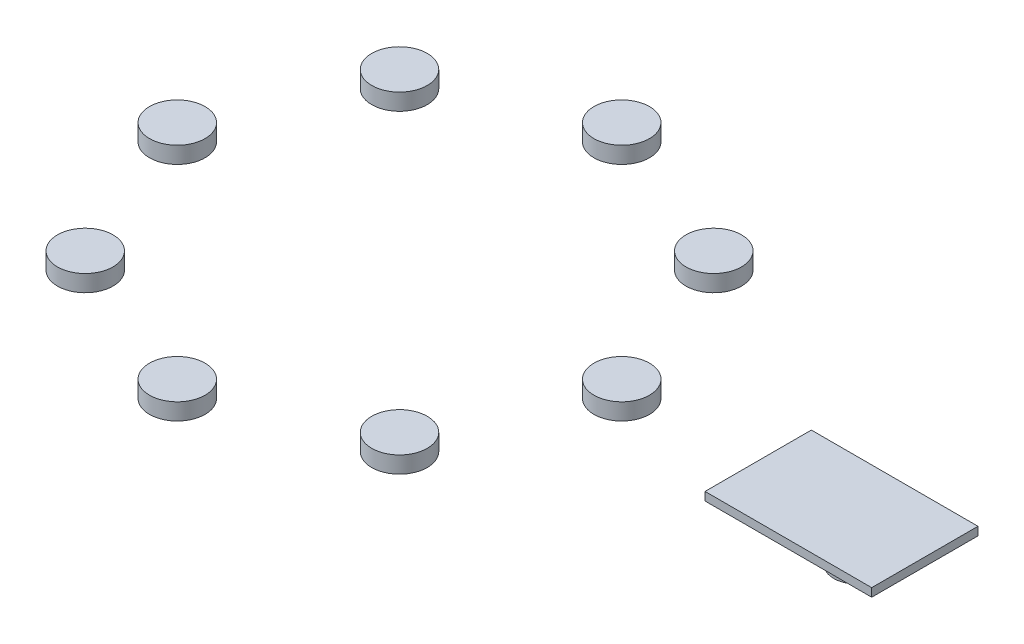
SolidWorks part; units mm, degrees
ref_plane "Front Plane" through (0, 0, 0) normal (0, 0, 1) x (1, 0, 0)
ref_plane "Top Plane" through (0, 0, 0) normal (0, 1, 0) x (1, 0, 0)
ref_plane "Right Plane" through (0, 0, 0) normal (1, 0, 0) x (0, 0, -1)
sketch "Sketch1" plane through (0, 0, 0) normal (0, 1, 0) x (1, 0, 0)
  line L0 (-37.5, 0) -> (-15, 0) construction
  line L7 (32.5, -5) -> (17.5, -5)
  line L8 (32.5, -5) -> (32.5, 4.5667)
  line L9 (32.5, 4.5667) -> (17.5, 4.5667)
  line L10 (17.5, -5) -> (17.5, 4.5667)
  line L11 (32.5, -5) -> (17.5, 4.5667) construction
  line L12 (32.5, 4.5667) -> (17.5, -5) construction
  circle A0 centre (-35, 0) radius 2.5
  circle A2 centre (-29.1421, 14.1421) radius 2.5
  circle A3 centre (-15, 20) radius 2.5
  circle A4 centre (-0.8579, 14.1421) radius 2.5
  circle A5 centre (5, 0) radius 2.5
  circle A6 centre (-0.8579, -14.1421) radius 2.5
  circle A7 centre (-15, -20) radius 2.5
  circle A8 centre (-29.1421, -14.1421) radius 2.5
  point P0 (0, 0)
  point P6 (25, -0.2166)
  dimension "D3" = 5
  dimension "D6" = 22.5
  dimension "D9" = 15
  dimension "D7" = 8
extrude "Boss-Extrude3" add sketch "Sketch1" along normal blind 1.5 contours A5 | A7 | A8 | A0 | L10 L7 L8 L9 | A2 | A3 | A4 | A6 region at (25, 0, 0.2166) region at (-35, 0, 0) region at (-29.1421, 0, -14.1421) region at (5, 0, 0) region at (-15, 0, 20) region at (-29.1421, 0, 14.1421)
sketch "Sketch2" plane through (0, 0, 0) normal (0, -1, 0) x (1, 0, 0)
  line L0 (17.5, -4.5667) -> (32.5, 5)
  line L1 (32.5, 5) -> (17.5, 5) construction
  line L2 (32.5, 5) -> (32.5, -4.5667) construction
  line L3 (32.5, -4.5667) -> (17.5, -4.5667) construction
  line L6 (17.5, 5) -> (32.5, 5)
  line L7 (17.5, 5) -> (17.5, -4.5667)
  line L8 (17.5, -4.5667) -> (32.5, -4.5667)
  line L9 (32.5, 5) -> (32.5, -4.5667)
  circle A0 centre (21.4198, -2.0667) radius 2
  circle A1 centre (28.5802, 2.5) radius 2
  line M1 (17.5, 5) -> (17.5, -4.5667)
  line M2 (17.5, -4.5667) -> (32.5, -4.5667)
  line M3 (32.5, -4.5667) -> (32.5, 5)
  line M4 (32.5, 5) -> (17.5, 5)
  dimension "D1" = 4
  dimension "D2" = 4
  dimension "D3" = 2.5
  dimension "D4" = 2.5
extrude "Cut-Extrude1" cut sketch "Sketch2" against normal blind 0.75 contours A1 L0 A0 M4 M1 | A1 L0 A0 M2 M3 region at (22.0661, 0, 1.9977) region at (27.9339, 0, -1.5644)
